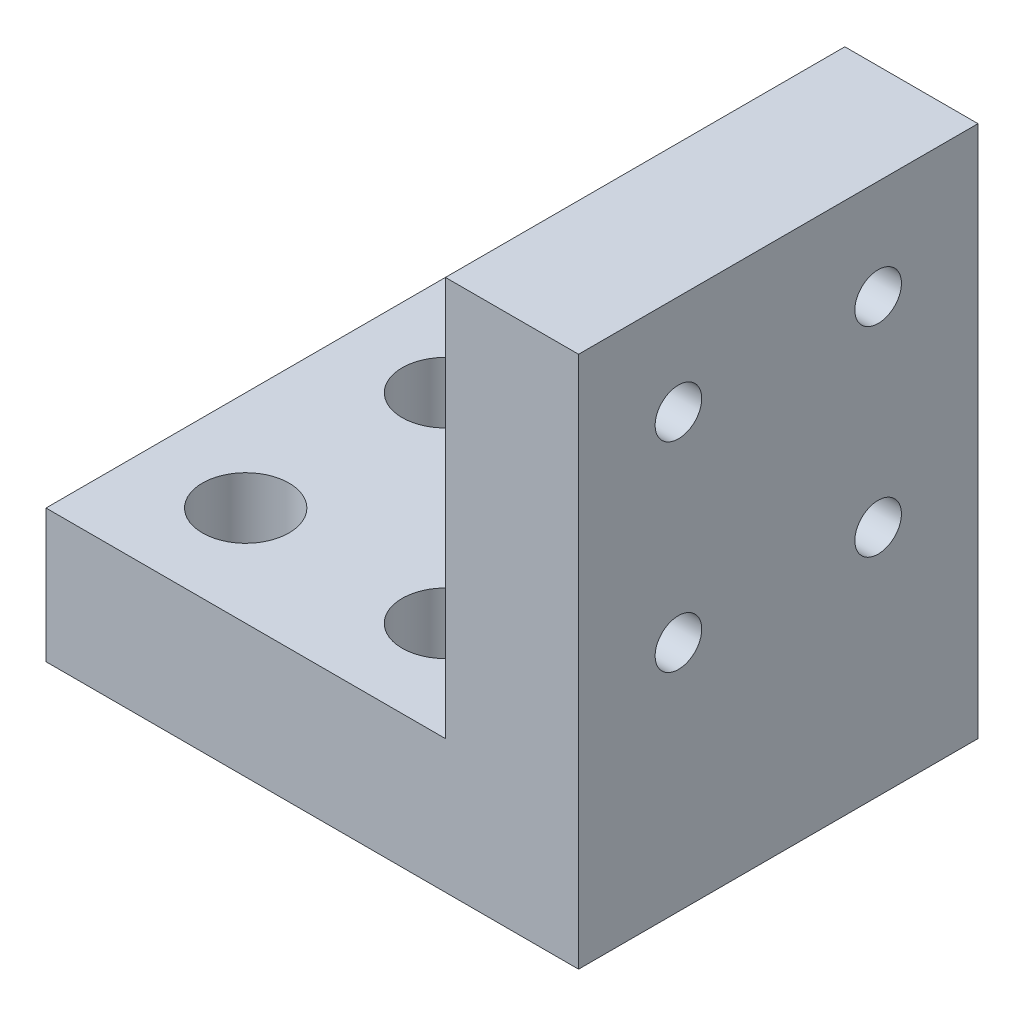
SolidWorks part; units mm, degrees
ref_plane "Plano frontal" through (0, 0, 0) normal (0, 0, 1) x (1, 0, 0)
ref_plane "Plano superior" through (0, 0, 0) normal (0, 1, 0) x (1, 0, 0)
ref_plane "Plano direito" through (0, 0, 0) normal (1, 0, 0) x (0, 0, -1)
sketch "Esboço1" plane through (0, 0, 0) normal (0, 1, 0) x (1, 0, 0)
  line L1 (0, 0) -> (40, 0)
  line L2 (0, 0) -> (0, 30)
  line L3 (0, 30) -> (40, 30)
  line L4 (40, 0) -> (40, 30)
  dimension "D1" = 30
  dimension "D2" = 40
extrude "Ressalto-extrusão1" add sketch "Esboço1" along normal blind 10
sketch "Esboço2" plane through (0, 10, 0) normal (0, 1, 0) x (1, 0, 0)
  line L0 (0, 0) -> (40, 0) construction
  line L1 (40, 30) -> (30, 30)
  line L2 (40, 30) -> (40, 0)
  line L3 (40, 0) -> (30, 0)
  line L4 (30, 30) -> (30, 0)
  dimension "D1" = 10
extrude "Ressalto-extrusão2" add sketch "Esboço2" along normal blind 30
sketch "Esboço4" plane through (0, 10, 0) normal (0, 1, 0) x (1, 0, 0)
  line L0 (0, 30) -> (0, 0) construction
  line L1 (0, 15) -> (30, 15) construction
  line L2 (30, 30) -> (30, 0) construction
  line L3 (30, 30) -> (0, 30) construction
  circle A0 centre (7.5, 22.5) radius 3.25
  circle A1 centre (22.5, 22.5) radius 3.25
  circle A2 centre (22.5, 7.5) radius 3.25
  circle A3 centre (7.5, 7.5) radius 3.25
  dimension "D5" = 6.5
  dimension "D6" = 15
  dimension "D1" = 7.5
  dimension "D2" = 7.5
  dimension "D7" = 15
  dimension "D3" = 2
  dimension "D4" = 2
extrude "Corte-extrusão1" cut sketch "Esboço4" against normal blind 6
sketch "Esboço5" plane through (0, 10, 0) normal (0, 1, 0) x (1, 0, 0)
  circle A0 centre (7.5, 22.5) radius 1.75
  circle A1 centre (22.5, 22.5) radius 1.75
  circle A2 centre (22.5, 7.5) radius 1.75
  circle A3 centre (7.5, 7.5) radius 1.75
  dimension "D1" = 3.5
  dimension "D2" = 2
  dimension "D3" = 2
extrude "Corte-extrusão2" cut sketch "Esboço5" against normal up to surface (10 mm away) up to face at (20, 0, -15)
sketch "Esboço6" plane through (30, 0, 0) normal (-1, 0, 0) x (0, 0, 1)
  line L0 (-15, 40) -> (-15, 10) construction
  line L1 (-30, 40) -> (0, 40) construction
  line L2 (-30, 10) -> (0, 10) construction
  line L3 (0, 40) -> (0, 10) construction
  circle A0 centre (-7.5, 32.5) radius 3.25
  circle A1 centre (-22.5, 32.5) radius 3.25
  circle A2 centre (-22.5, 17.5) radius 3.25
  circle A3 centre (-7.5, 17.5) radius 3.25
  dimension "D1" = 6.5
  dimension "D2" = 7.5
  dimension "D3" = 7.5
  dimension "D4" = 2
  dimension "D5" = 2
extrude "Corte-extrusão3" cut sketch "Esboço6" against normal blind 6
sketch "Esboço7" plane through (30, 0, 0) normal (-1, 0, 0) x (0, 0, 1)
  circle A0 centre (-22.5, 32.5) radius 1.75
  circle A1 centre (-7.5, 32.5) radius 1.75
  circle A2 centre (-7.5, 17.5) radius 1.75
  circle A3 centre (-22.5, 17.5) radius 1.75
  dimension "D1" = 3.5
  dimension "D2" = 2
  dimension "D3" = 2
extrude "Corte-extrusão4" cut sketch "Esboço7" against normal up to surface (10 mm away) up to face at (40, 20, -15)
